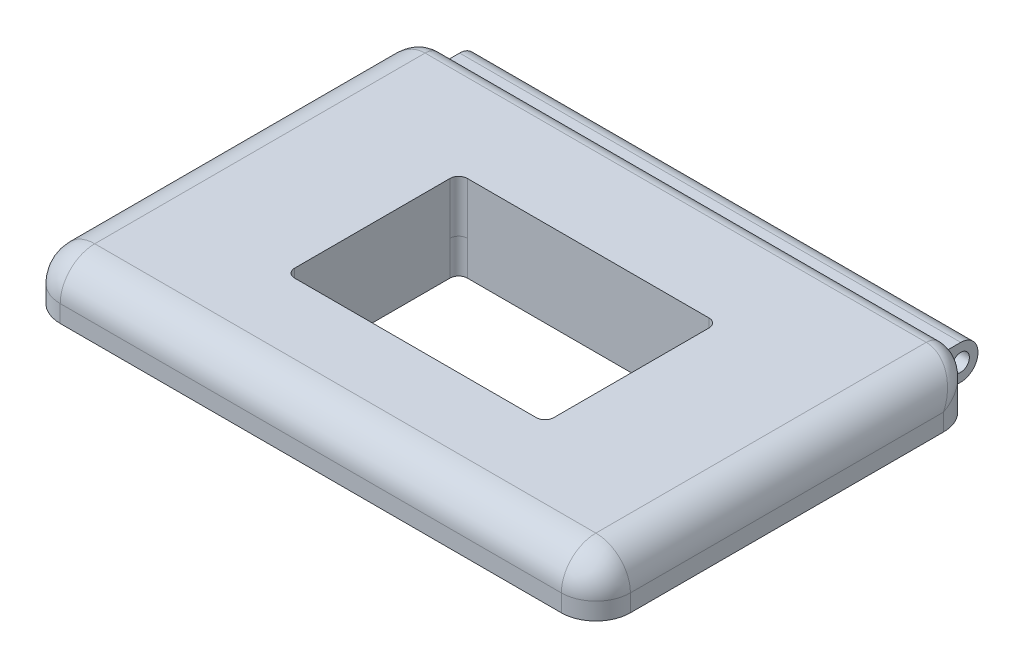
SolidWorks part; units mm, degrees
ref_plane "Front Plane" through (0, 0, 0) normal (0, 0, 1) x (1, 0, 0)
ref_plane "Top Plane" through (0, 0, 0) normal (0, 1, 0) x (1, 0, 0)
ref_plane "Right Plane" through (0, 0, 0) normal (1, 0, 0) x (0, 0, -1)
sketch "Sketch1" plane through (0, 0, 0) normal (0, 1, 0) x (1, 0, 0)
  line L1 (-165.1, -110.65) -> (165.1, -110.65)
  line L2 (-165.1, -110.65) -> (-165.1, 110.65)
  line L3 (-165.1, 110.65) -> (165.1, 110.65)
  line L4 (165.1, -110.65) -> (165.1, 110.65)
  line L5 (-165.1, -110.65) -> (165.1, 110.65) construction
  line L6 (-165.1, 110.65) -> (165.1, -110.65) construction
  point P0 (0, 0)
  dimension "D1" = 330.2
  dimension "D2" = 221.3
extrude "Boss-Extrude1" add sketch "Sketch1" along normal blind 30
sketch "Sketch3" plane through (0, 0, 0) normal (0, -1, 0) x (1, 0, 0)
  line L2 (165.1, -110.65) -> (-165.1, -110.65) construction
  line L3 (-137.29, -110.65) -> (137.284, -110.65)
  line L4 (-137.29, -110.65) -> (-137.29, 87.724)
  line L5 (-137.29, 87.724) -> (137.284, 87.724)
  line L6 (137.284, -110.65) -> (137.284, 87.724)
  point P0 (0, 0)
  dimension "D1" = 274.574
  dimension "D2" = 198.374
  dimension "D3" = 137.29
extrude "Boss-Extrude2" add sketch "Sketch3" along normal blind 20 draft 3
fillet "Fillet3" radius 10 rebuild error yes
sketch "Sketch4" plane through (0, 30, 0) normal (0, 1, 0) x (1, 0, 0)
  line L1 (-75, -50) -> (75, -50)
  line L2 (-75, -50) -> (-75, 50)
  line L3 (-75, 50) -> (75, 50)
  line L4 (75, -50) -> (75, 50)
  line L5 (-75, -50) -> (75, 50) construction
  line L6 (-75, 50) -> (75, -50) construction
  point P0 (0, 0)
  dimension "D1" = 150
  dimension "D2" = 100
extrude "Cut-Extrude2" cut sketch "Sketch4" against normal blind 60
fillet "Fillet4" radius 5 4 edges at (-75, 5, 50) (-75, 5, -50) (75, 5, 50) (75, 5, -50)
fillet "Fillet5" radius 20 7 edges at (-165.1, 15, -110.65) (-165.1, 30, 0) (-165.1, 15, 110.65) (165.1, 15, 110.65) (0, 30, 110.65) (165.1, 30, 0) (165.1, 15, -110.65)
ref_plane "Plane1" through (145.1, 0, 0) normal (1, 0, 0) x (0, -1, 0)
sketch "Sketch5" plane through (145.1, 0, 0) normal (1, 0, 0) x (0, -1, 0)
  line L0 (0, 90.65) -> (0, 110.65) construction
  line L1 (-30, 110.65) -> (0, 110.65) construction
  line L2 (-20, 120.65) -> (-20, 110.65)
  line L3 (-20, 110.65) -> (0, 110.65)
  line L4 (0, 110.65) -> (0, 120.65)
  arc A0 (0, 120.65) -> (-20, 120.65) centre (-10, 120.65) ccw
  circle A1 centre (-10, 120.65) radius 5
  dimension "D1" = 10
  dimension "D2" = 20
  dimension "D3" = 10
  dimension "D4" = 10
extrude "Boss-Extrude3" add sketch "Sketch5" against normal blind 290.2
fillet "Fillet6" radius 10 3 edges at (159.2421, 24.1421, -104.7921) (-159.2421, 24.1421, -104.7921) (0, 30, -110.65)
fillet "Fillet7" radius 10 8 edges at (-136.7659, -10, 87.1999) (136.7599, -10, 87.1999) (-0.003, -20, -109.6018) (136.2358, -20, -11.463) (-0.003, -20, 86.6758) (-136.2418, -20, -11.463)
sketch "Sketch2" plane through (0, 30, 0) normal (0, 1, 0) x (1, 0, 0)
  line L1 (-75, 50) -> (75, 50)
  line L2 (-75, 50) -> (-75, -50)
  line L3 (-75, -50) -> (75, -50)
  line L4 (75, 50) -> (75, -50)
  line L5 (-75, 50) -> (75, -50) construction
  line L6 (-75, -50) -> (75, 50) construction
  point P0 (0, 0)
  dimension "D1" = 150
  dimension "D2" = 100
extrude "Cut-Extrude1" cut sketch "Sketch2" against normal blind 30
fillet "Fillet1" radius 5 4 edges at (75, 15, 50) (75, 15, -50) (-75, 15, 50) (-75, 15, -50)
fillet "Fillet2" radius 20 rebuild error yes
